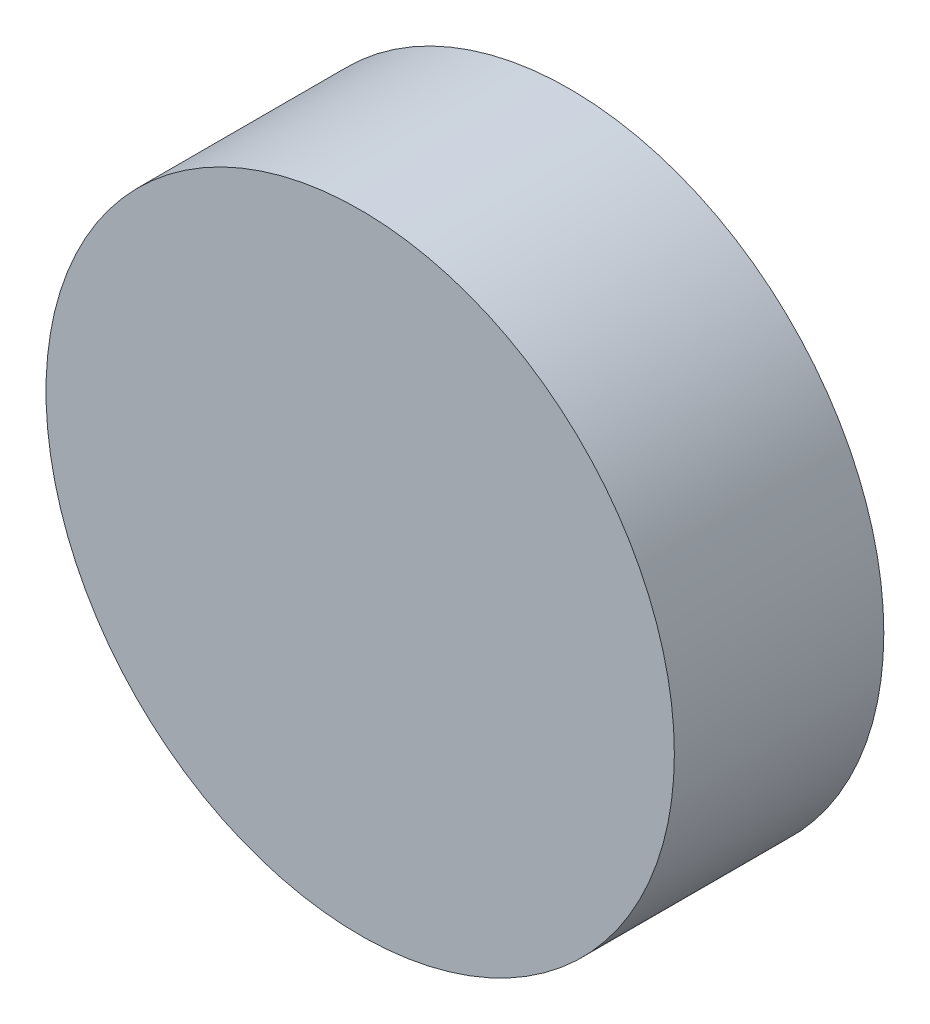
SolidWorks part; units mm, degrees
ref_plane "前视基准面" through (0, 0, 0) normal (0, 0, 1) x (1, 0, 0)
ref_plane "上视基准面" through (0, 0, 0) normal (0, 1, 0) x (1, 0, 0)
ref_plane "右视基准面" through (0, 0, 0) normal (1, 0, 0) x (0, 0, -1)
other "Configuration Table"
sketch "Sketch1" plane through (0, 0, 0) normal (0, 0, 1) x (1, 0, 0)
  circle A0 centre (0, 0) radius 75
extrude "Boss-Extrude1" add sketch "Sketch1" along normal blind 50
ref_plane "mount_face_top" through (0, 0, 50) normal (0, 0, 1) x (1, 0, 0)
ref_plane "base_face_bottom" through (0, 0, 0) normal (0, 0, 1) x (1, 0, 0)
sketch3d "3DSketch1"
  line L0 (0, 0, 0) -> (0, 0, 50) construction
ref_axis "main_axis_z" through (0, 0, 0) along (0, 0, 1)
